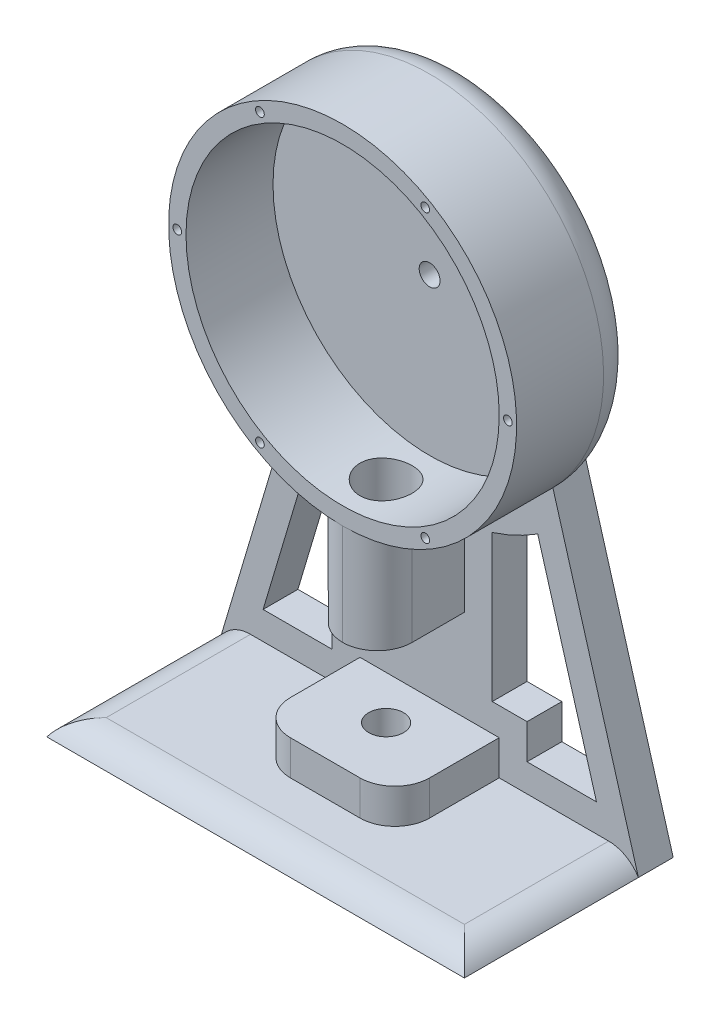
SolidWorks part; units mm, degrees
ref_plane "Front Plane" through (0, 0, 0) normal (0, 0, 1) x (1, 0, 0)
ref_plane "Top Plane" through (0, 0, 0) normal (0, 1, 0) x (1, 0, 0)
ref_plane "Right Plane" through (0, 0, 0) normal (1, 0, 0) x (0, 0, -1)
sketch "Sketch1" plane through (0, 0, 0) normal (0, 0, 1) x (1, 0, 0)
  line L0 (0, 0) -> (0, 180) construction
  line L1 (0, -55) -> (0, 55) construction
  line L2 (0, 0) -> (25.0873, 84.2075)
  line L3 (0, 0) -> (120, 0)
  line L4 (55, 0) -> (-55, 0) construction
  line L5 (35, 120) -> (35, 0) construction
  line L6 (120, 0) -> (95.4233, 84.7128)
  line L7 (85, 120) -> (85, 0) construction
  line L8 (35, 120) -> (85, 120) construction
  line L9 (60, 120) -> (60, 0) construction
  arc A1 (95.4233, 84.7128) -> (25.0873, 84.2075) centre (60, 120) ccw
  dimension "D2" = 50
  dimension "D6" = 50
  dimension "D1" = 90
  dimension "D3" = 87.8651
  dimension "D4" = 120
  dimension "D5" = 35
  dimension "D7" = 73.822
extrude "Boss-Extrude1" add sketch "Sketch1" along normal blind 10
sketch "Sketch2" plane through (0, 0, 10) normal (0, 0, 1) x (1, 0, 0)
  line L0 (60, 120) -> (60, 75) construction
  line L1 (60, 75) -> (60, 70) construction
  line L2 (50, 41.0102) -> (70, 41.0102)
  line L3 (50, 41.0102) -> (50, 71.0102)
  line L5 (70, 71.0102) -> (70, 41.0102)
  arc A0 (70, 71.0102) -> (50, 71.0102) centre (60, 120) ccw
  circle A2 centre (60, 120) radius 45
  dimension "D1" = 10
  dimension "D3" = 90
  dimension "D2" = 10
  dimension "D4" = 30
extrude "Boss-Extrude2" add sketch "Sketch2" along normal blind 25 and the other way blind 5
sketch "Sketch5" plane through (0, 0, 10) normal (0, 0, 1) x (1, 0, 0)
  line L0 (0, 0) -> (120, 0)
  line L1 (120, 0) -> (118.6069, 4.802)
  line L2 (120, 0) -> (95.4233, 84.7128) construction
  line L3 (0, 0) -> (1.4276, 4.7919)
  line L4 (25.0873, 84.2075) -> (0, 0) construction
  line L5 (1.4276, 4.7919) -> (118.6069, 4.802)
extrude "Boss-Extrude3" add sketch "Sketch5" along normal blind 50
sketch "Sketch6" plane through (0, 0, 10) normal (0, 0, 1) x (1, 0, 0)
  line L0 (118.6069, 4.802) -> (1.4276, 4.7919) construction
  line L1 (40, 4.7952) -> (80, 4.7952)
  line L2 (40, 4.7952) -> (40, 14.7952)
  line L3 (40, 14.7952) -> (80, 14.7952)
  line L4 (80, 4.7952) -> (80, 14.7952)
  line L7 (50, 41.0102) -> (50, 14.7952) construction
  line L8 (70, 41.0102) -> (70, 14.7952) construction
  dimension "D1" = 10
  dimension "D2" = 10
  dimension "D3" = 10
extrude "Boss-Extrude4" add sketch "Sketch6" along normal blind 30
sketch "Sketch7" plane through (0, 0, 10) normal (0, 0, 1) x (1, 0, 0)
  circle A0 centre (60, 120) radius 3
  dimension "D1" = 6
extrude "Cut-Extrude3" cut sketch "Sketch7" against normal blind 10
sketch "Sketch8" plane through (0, 0, 35) normal (0, 0, 1) x (1, 0, 0)
  line L0 (10, 120) -> (15, 120) construction
  arc A1 (70, 71.0102) -> (50, 71.0102) centre (60, 120) ccw construction
  circle A2 centre (60, 120) radius 45 construction
  circle A3 centre (60, 120) radius 45 construction
  circle A4 centre (12.5, 120) radius 1.25
  dimension "D1" = 2.5
extrude "Cut-Extrude4" cut sketch "Sketch8" against normal blind 7
pattern_circular "CirPattern1" count 6 every 60 about axis through (60, 120, 10) along (0, 0, 1) of "Cut-Extrude4"
fillet "Fillet1" radius 10 5 edges at (80, 9.7969, 40) (40, 9.7952, 40) (60.0172, 4.7969, 60) (118.6069, 4.802, 35) (1.4276, 4.7919, 35)
fillet "Fillet2" radius 10 2 edges at (70, 56.0102, 35) (50, 56.0102, 35)
fillet "Fillet3" radius 10 1 edges at (59.6408, 169.9987, 0)
sketch "Sketch3" plane through (0, 41.0102, 0) normal (0, -1, 0) x (1, 0, 0)
  line L0 (50, 35) -> (70, 35) construction
  line L2 (50, 10) -> (50, 25) construction
  circle A0 centre (60, 22.5) radius 5
  dimension "D1" = 10
  dimension "D2" = 12.5
  dimension "D3" = 10
extrude "Cut-Extrude1" cut sketch "Sketch3" against normal blind 10 and the other way blind 54
sketch "Sketch4" plane through (0, 51.0102, 0) normal (0, -1, 0) x (1, 0, 0)
  circle A0 centre (60, 22.5) radius 7.5
  dimension "D1" = 15
extrude "Cut-Extrude2" cut sketch "Sketch4" against normal blind 26
sketch "Sketch11" plane through (0, 0, 10) normal (0, 0, 1) x (1, 0, 0)
  line L20 (42, 33.0102) -> (42, 22.7952)
  line L21 (78, 33.0102) -> (78, 22.7952)
  line L30 (12.1587, 12.7928) -> (32, 12.7945)
  line L31 (32, 12.7945) -> (32, 22.7952)
  line L32 (32, 22.7952) -> (88, 22.7952)
  line L33 (88, 22.7952) -> (88, 12.7993)
  line L34 (88, 12.7993) -> (107.9563, 12.8011)
  line L35 (107.9563, 12.8011) -> (91.0657, 71.0212)
  line L36 (78, 64.8638) -> (78, 33.0102)
  line L37 (78, 33.0102) -> (42, 33.0102)
  line L38 (42, 33.0102) -> (42, 64.8638)
  line L39 (29.4162, 70.7188) -> (12.1587, 12.7928)
  line L40 (12.1587, 12.7928) -> (32, 12.7945)
  line L41 (32, 12.7945) -> (32, 22.7952)
  line L42 (32, 22.7952) -> (88, 22.7952)
  line L43 (88, 22.7952) -> (88, 12.7993)
  line L44 (88, 12.7993) -> (107.9563, 12.8011)
  line L45 (107.9563, 12.8011) -> (91.0657, 71.0212)
  line L46 (78, 64.8638) -> (78, 33.0102)
  line L47 (78, 33.0102) -> (42, 33.0102)
  line L48 (42, 33.0102) -> (42, 64.8638)
  line L49 (29.4162, 70.7188) -> (12.1587, 12.7928)
  line L56 (45, 22.7952) -> (75, 22.7952)
  arc A12 (78, 64.8638) -> (91.0657, 71.0212) centre (60, 120) ccw
  arc A13 (29.4162, 70.7188) -> (42, 64.8638) centre (60, 120) ccw
  arc A14 (78, 64.8638) -> (91.0657, 71.0212) centre (60, 120) ccw
  arc A15 (29.4162, 70.7188) -> (42, 64.8638) centre (60, 120) ccw
  dimension "D1" = 8
extrude "Cut-Extrude6" cut sketch "Sketch11" against normal blind 10 contours A15 L49 L40 L41 L42 L20 L48 | A14 L46 L21 L42 L43 L44 L45
